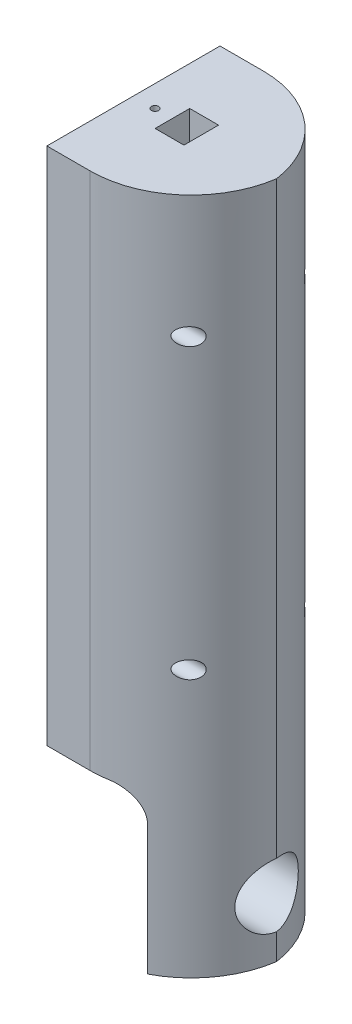
SolidWorks part; units mm, degrees
ref_plane "Plan de face" through (0, 0, 0) normal (0, 0, 1) x (1, 0, 0)
ref_plane "Plan de dessus" through (0, 0, 0) normal (0, 1, 0) x (1, 0, 0)
ref_plane "Plan de droite" through (0, 0, 0) normal (1, 0, 0) x (0, 0, -1)
sketch "Esquisse1" plane through (0, 0, 0) normal (0, 0, 1) x (1, 0, 0)
  line L0 (-50, 175) -> (-50, -55)
  line L1 (-50, -55) -> (-31, -55)
  line L2 (-31, -55) -> (-31, 0)
  line L3 (-31, 0) -> (31, 0)
  line L4 (31, 0) -> (31, -55)
  line L5 (31, -55) -> (50, -55)
  line L6 (50, -55) -> (50, 175)
  line L7 (50, 175) -> (-50, 175)
  line L8 (0, 0) -> (50, 0) construction
  line L9 (0, 0) -> (0, 175) construction
  point P14 (0, 0)
  dimension "D1" = 230
  dimension "D2" = 100
  dimension "D3" = 62
  dimension "D4" = 55
extrude "Boss.-Extru.1" add sketch "Esquisse1" along normal blind 60
fillet "Congé4" radius 35 1 edges at (-50, 60, 60)
fillet "Congé5" radius 35 1 edges at (-50, 60, 0)
fillet "Congé6" radius 35 2 edges at (50, 60, 0) (50, 60, 60)
fillet "Congé12" radius 10 2 edges at (-31, 0, 29.6462) (31, 0, 30)
sketch "Esquisse3" plane through (31, 0, 0) normal (-1, 0, 0) x (0, 0, 1)
  line L0 (30, -55) -> (30, -35) construction
  line L1 (56.1288, -55) -> (3.8712, -55) construction
  circle A1 centre (30, -35) radius 11
  dimension "D1" = 22
  dimension "D2" = 20
extrude "Enlèv. mat.-Extru.4" cut sketch "Esquisse3" against normal blind 50
sketch "Esquisse5" plane through (0, 175, 0) normal (0, 1, 0) x (1, 0, 0)
  line L0 (0, -60) -> (0, 0)
  line L1 (15, -60) -> (-15, -60) construction
  arc A0 (0, -60) -> (0, 0) centre (-29.0756, -30) cw
extrude "Enlèv. mat.-Extru.8" cut sketch "Esquisse5" against normal blind 251
sketch "Esquisse6" plane through (0, 0, 0) normal (-1, 0, 0) x (0, 0, 1)
  line L0 (30, 175) -> (30, 0) construction
  line L1 (60, 175) -> (0, 175) construction
  line L2 (60, 0) -> (0, 0) construction
  line L4 (60, 0) -> (60, 175) construction
  line L5 (60, 87.5) -> (0, 87.5) construction
  line L6 (0, 0) -> (0, 175) construction
  circle A0 centre (10, 137.5) radius 2
  circle A1 centre (50, 137.5) radius 2
  circle A2 centre (50, 37.5) radius 2
  circle A3 centre (10, 37.5) radius 2
  dimension "D1" = 40
  dimension "D2" = 50
  dimension "D3" = 4
extrude "Enlèv. mat.-Extru.9" cut sketch "Esquisse6" against normal blind 58
sketch "Esquisse13" plane through (0, 175, 0) normal (0, 1, 0) x (1, 0, 0)
  line L0 (0, 0) -> (0, -60) construction
  line L1 (0, -30) -> (49.641, -30) construction
  line L2 (13.5, -24) -> (13.5, -36)
  line L3 (13.5, -36) -> (23.5, -36)
  line L4 (23.5, -36) -> (23.5, -24)
  line L5 (23.5, -24) -> (13.5, -24)
  point P9 (13.5, -30)
  dimension "D1" = 13.5
  dimension "D2" = 12
  dimension "D3" = 10
extrude "Enlèv. mat.-Extru.15" cut sketch "Esquisse13" against normal through all
shell "Coque1" thickness 5 removed face at (18.5, 175, 30)
ref_plane "Plan2" through (49.641, 0, 0) normal (-1, 0, 0) x (0, 0, 1)
sketch "Esquisse11" plane through (49.641, 0, 0) normal (-1, 0, 0) x (0, 0, 1)
  circle A0 centre (50, 37.5) radius 2 construction
  circle A1 centre (50, 137.5) radius 2 construction
  circle A2 centre (50, 37.5) radius 2 construction
  circle A3 centre (50, 137.5) radius 2 construction
  circle A4 centre (10, 137.5) radius 2 construction
  circle A5 centre (10, 37.5) radius 2 construction
  circle A6 centre (10, 137.5) radius 2 construction
  circle A7 centre (10, 37.5) radius 2 construction
  circle A8 centre (50, 137.5) radius 3
  circle A9 centre (10, 137.5) radius 3
  circle A10 centre (50, 37.5) radius 3
  circle A11 centre (10, 37.5) radius 3
  dimension "D1" = 1
  dimension "D2" = 1
  dimension "D3" = 1
  dimension "D4" = 1
extrude "Enlèv. mat.-Extru.14" cut sketch "Esquisse11" along normal up to vertex up to point (15, 0, 0)
sketch "Esquisse12" plane through (0, 175, 0) normal (0, 1, 0) x (1, 0, 0)
  line L0 (15, 0) -> (0, 0) construction
  line L1 (0, -60) -> (0, 0) construction
  line L2 (13.5, -24) -> (13.5, -36) construction
  line L3 (15, -60) -> (0, -60) construction
  line L4 (15, 0) -> (0, 0)
  line L5 (0, -60) -> (0, 0)
  line L7 (15, -60) -> (0, -60)
  line L9 (13.5, -36) -> (23.5, -36) construction
  line L10 (23.5, -36) -> (23.5, -24) construction
  line L11 (23.5, -24) -> (13.5, -24) construction
  line L12 (13.5, -24) -> (13.5, -36)
  line L13 (13.5, -36) -> (23.5, -36)
  line L14 (23.5, -36) -> (23.5, -24)
  line L15 (23.5, -24) -> (13.5, -24)
  arc A1 (15, -60) -> (49.641, -30) centre (15, -25) ccw construction
  arc A2 (49.641, -30) -> (15, 0) centre (15, -35) ccw construction
  arc A4 (15, -60) -> (49.641, -30) centre (15, -25) ccw
  arc A5 (49.641, -30) -> (15, 0) centre (15, -35) ccw
extrude "Boss.-Extru.2" add sketch "Esquisse12" along normal blind 5
ref_plane "Plan3" through (0, 0, 30) normal (0, 0, -1) x (0, -1, 0)
sketch "Esquisse14" plane through (0, 180, 0) normal (0, 1, 0) x (1, 0, 0)
  line L0 (0, 0) -> (0, -60) construction
  line L1 (0, -30) -> (7.5, -30) construction
  circle A0 centre (7.5, -30) radius 1.25
  dimension "D2" = 2.5
  dimension "D1" = 7.5
extrude "Enlèv. mat.-Extru.16" cut sketch "Esquisse14" against normal blind 4 contours A0
